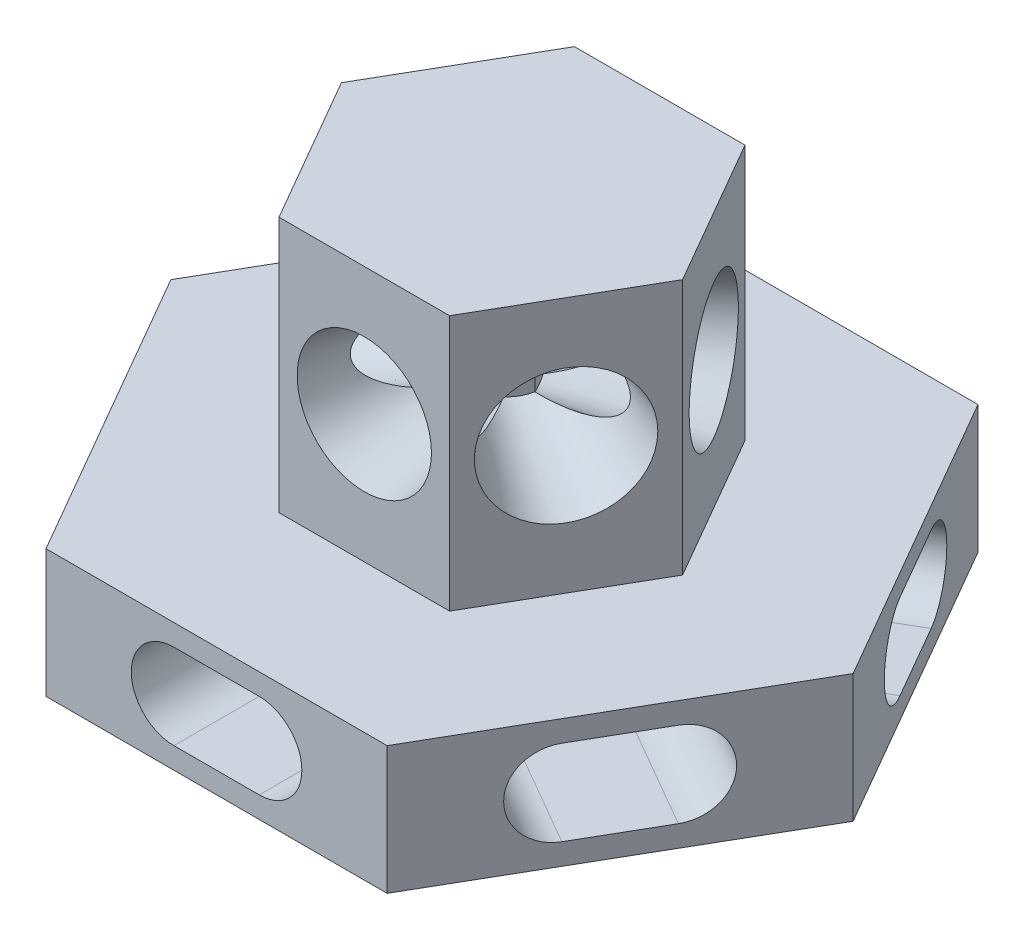
SolidWorks part; units mm, degrees
ref_plane "Front Plane" through (0, 0, 0) normal (0, 0, 1) x (1, 0, 0)
ref_plane "Top Plane" through (0, 0, 0) normal (0, 1, 0) x (1, 0, 0)
ref_plane "Right Plane" through (0, 0, 0) normal (1, 0, 0) x (0, 0, -1)
sketch "Sketch1" plane through (0, 0, 0) normal (0, 1, 0) x (1, 0, 0)
  line L0 (-40, 69.282) -> (40, -69.282) construction
  line L1 (40, -69.282) -> (80, 0)
  line L2 (80, 0) -> (40, 69.282)
  line L3 (40, 69.282) -> (-40, 69.282)
  line L4 (-40, 69.282) -> (-80, 0)
  line L5 (-80, 0) -> (-40, -69.282)
  line L6 (-40, -69.282) -> (40, -69.282)
  line L7 (-80, 0) -> (80, 0) construction
  line L8 (40, 69.282) -> (-40, -69.282) construction
  point P0 (0, 0)
  dimension "D1" = 80
extrude "Boss-Extrude1" add sketch "Sketch1" along normal blind 30
sketch "Sketch2" plane through (0, 30, 0) normal (0, 1, 0) x (1, 0, 0)
  line L9 (20, -34.641) -> (40, 0)
  line L10 (40, 0) -> (20, 34.641)
  line L11 (20, 34.641) -> (-20, 34.641)
  line L12 (-20, 34.641) -> (-40, 0)
  line L13 (-40, 0) -> (-20, -34.641)
  line L14 (-20, -34.641) -> (20, -34.641)
  circle A0 centre (0, 0) radius 34.641 construction
  dimension "D1" = 40
sketch "Sketch3" plane through (60, 0, 34.641) normal (0.866, 0, 0.5) x (0.5, 0, -0.866)
  line L0 (0, 0) -> (0, 59.5479) construction
  line L1 (-10, 15) -> (10, 15) construction
  line L2 (-10, 25) -> (10, 25)
  line L3 (-10, 5) -> (10, 5)
  line L4 (-40, 0) -> (40, 0) construction
  arc A0 (-10, 25) -> (-10, 5) centre (-10, 15) ccw
  arc A1 (10, 5) -> (10, 25) centre (10, 15) ccw
  point P5 (0, 15)
  point P10 (0, 0)
  dimension "D2" = 10
  dimension "D1" = 20
  dimension "D3" = 15
ref_axis "Axis1" through (0, -4.5, 0) along (0, 1, 0)
extrude "Boss-Extrude3" add sketch "Sketch2" along normal blind 60
sketch "Sketch8" plane through (30, 0, 17.3205) normal (0.866, 0, 0.5) x (0.5, 0, -0.866)
  line L0 (-20, 90) -> (20, 90) construction
  line L1 (20, 90) -> (20, 30) construction
  circle A0 centre (0, 60) radius 15.75
  dimension "D1" = 31.5
  dimension "D2" = 30
  dimension "D3" = 20
extrude "Cut-Extrude3" cut sketch "Sketch8" against normal blind 30 draft 10
ref_axis "Axis3" through (0, -4.5, 0) along (0, 1, 0)
pattern_circular "CirPattern4" count 6 over 360 about axis through (0, -4.5, 0) along (0, 1, 0) of "Cut-Extrude3"
extrude "Cut-Extrude4" cut sketch "Sketch3" against normal blind 44
pattern_circular "CirPattern6" count 6 over 360 about axis through (0, -4.5, 0) along (0, 1, 0) of "Cut-Extrude4"
